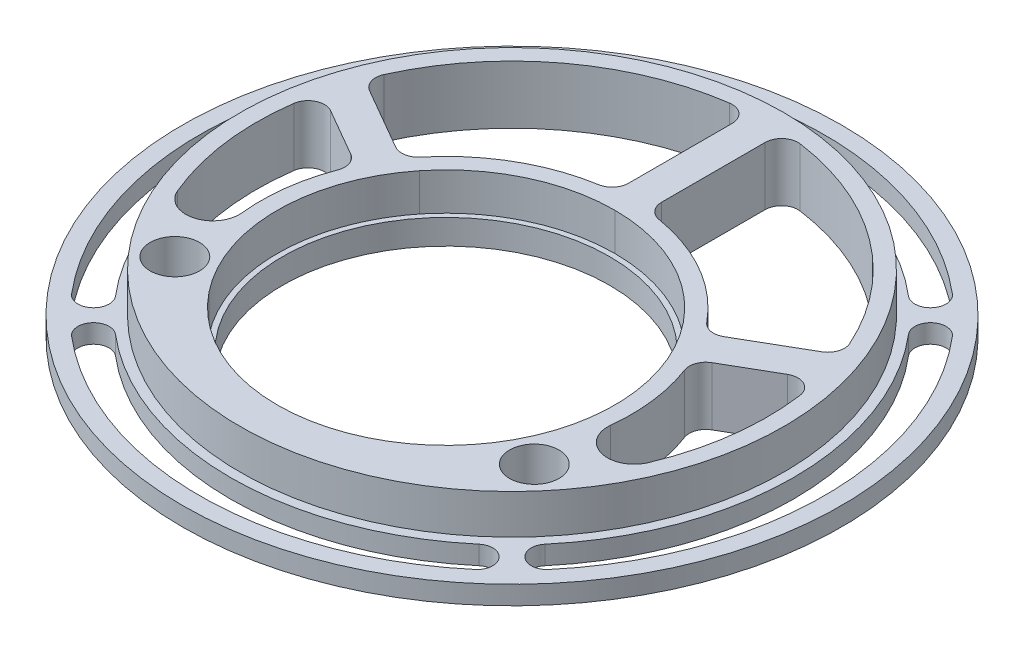
SolidWorks part; units mm, degrees
material "6061-T6 (SS)"
ref_plane "X-Y Datum" through (0, 0, 0) normal (0, 0, 1) x (1, 0, 0)
ref_plane "X-Z Datum" through (0, 0, 0) normal (0, 1, 0) x (1, 0, 0)
ref_plane "Y-Z Datum" through (0, 0, 0) normal (1, 0, 0) x (0, 0, -1)
sketch "Sketch1" plane through (0, 0, 0) normal (0, 1, 0) x (1, 0, 0)
  line L0 (0, 0) -> (0, -12.7) construction
  line L1 (0, -43.0151) -> (0, 43.0151) construction
  line L2 (0, 52.3875) -> (0, 61.9125) construction
  circle A0 centre (0, -12.7) radius 30.988
  circle A1 centre (0, 0) radius 52.3875 construction
  circle A2 centre (0, 0) radius 61.9125
  circle A3 centre (0, 0) radius 57.15 construction
  point P12 (0, 57.15)
  dimension "D2" = 61.976
  dimension "D3" = 104.775
  dimension "D4" = 123.825
  dimension "D5" = 114.3
  dimension "D1" = 12.7
extrude "Slotted-Body Extrude" add sketch "Sketch1" along normal blind 4.191 and the other way blind 0.2032
sketch "Sketch5" plane through (0, 4.191, 0) normal (0, 1, 0) x (1, 0, 0)
  circle A0 centre (0, 0) radius 52.3875 construction
  circle A1 centre (0, 0) radius 52.3875
extrude "Boss-Extrude3" add sketch "Sketch5" along normal blind 7.62
sketch "Sketch6" plane through (0, -0.2032, 0) normal (0, -1, 0) x (1, 0, 0)
  line L0 (0, -79.2756) -> (0, 0) construction
  circle A0 centre (0, 12.7) radius 30.988 construction
  circle A1 centre (0, 12.7) radius 30.988 construction
  circle A2 centre (0, 12.7) radius 32.512
  circle A21 centre (0, 0) radius 61.9125 construction
  dimension "D1" = 65.024
extrude "Cut-Extrude5" cut sketch "Sketch6" against normal through all
sketch "Sketch8" plane through (0, -0.2032, 0) normal (0, -1, 0) x (1, 0, 0)
  circle A0 centre (0, 12.7) radius 32.512 construction
  circle A1 centre (0, 12.7) radius 32.512
  circle A2 centre (0, 12.7) radius 31.496
  dimension "D1" = 62.992
extrude "Boss-Extrude4" add sketch "Sketch8" against normal blind 4.795 separate body
ref_point "Point1"
ref_plane "Plane1" through (0, 0, 0) normal (1, 0, 0) x (0, 0, -1)
split line "Split Line1"
ref_point "Point3"
ref_point "Point5"
ref_plane "Plane3" through (55.9011, 0, 0) normal (-1, 0, 0) x (0, 0, 1)
sketch "Sketch11" plane through (0, -0.2032, 0) normal (0, -1, 0) x (1, 0, 0)
  line L1 (-61.9125, -61.9125) -> (61.9125, -61.9125)
  line L2 (-61.9125, -61.9125) -> (-61.9125, 61.9125)
  line L3 (-61.9125, 61.9125) -> (61.9125, 61.9125)
  line L4 (61.9125, -61.9125) -> (61.9125, 61.9125)
  line L5 (-61.9125, -61.9125) -> (61.9125, 61.9125) construction
  line L6 (-61.9125, 61.9125) -> (61.9125, -61.9125) construction
  circle A0 centre (0, 0) radius 61.9125 construction
  point P0 (0, 0)
ref_point "Point6"
sketch "Sketch12" plane through (0, 4.191, 0) normal (0, 1, 0) x (1, 0, 0)
  line L0 (0, 0) -> (0, 57.2135)
  line L1 (0, -43.0151) -> (0, 43.0151) construction
  arc A0 (36.9549, 43.6775) -> (-36.9549, 43.6775) centre (0, 0) ccw construction
  arc A1 (38.8926, 45.9677) -> (-38.8926, 45.9677) centre (0, 0) ccw
  circle A2 centre (0, 0) radius 57.2135 construction
  arc A3 (-43.6775, 36.9549) -> (-43.6775, -36.9549) centre (0, 0) ccw construction
  arc A4 (-45.9677, 38.8926) -> (-45.9677, -38.8926) centre (0, 0) ccw
  arc A5 (-41.3872, 35.0171) -> (-41.3872, -35.0171) centre (0, 0) ccw
  arc A6 (-41.3872, 35.0171) -> (-45.9677, 38.8926) centre (-43.6775, 36.9549) ccw
  arc A7 (-45.9677, -38.8926) -> (-41.3872, -35.0171) centre (-43.6775, -36.9549) ccw
  arc A8 (35.0171, 41.3872) -> (-35.0171, 41.3872) centre (0, 0) ccw
  arc A9 (35.0171, 41.3872) -> (38.8926, 45.9677) centre (36.9549, 43.6775) ccw
  arc A10 (-38.8926, 45.9677) -> (-35.0171, 41.3872) centre (-36.9549, 43.6775) ccw
  arc A11 (43.6775, -36.9549) -> (43.6775, 36.9549) centre (0, 0) ccw construction
  arc A12 (45.9677, -38.8926) -> (45.9677, 38.8926) centre (0, 0) ccw
  arc A13 (41.3872, -35.0171) -> (41.3872, 35.0171) centre (0, 0) ccw
  arc A14 (41.3872, -35.0171) -> (45.9677, -38.8926) centre (43.6775, -36.9549) ccw
  arc A15 (45.9677, 38.8926) -> (41.3872, 35.0171) centre (43.6775, 36.9549) ccw
  arc A16 (-36.9549, -43.6775) -> (36.9549, -43.6775) centre (0, 0) ccw construction
  arc A17 (-38.8926, -45.9677) -> (38.8926, -45.9677) centre (0, 0) ccw
  arc A18 (-35.0171, -41.3872) -> (35.0171, -41.3872) centre (0, 0) ccw
  arc A19 (-35.0171, -41.3872) -> (-38.8926, -45.9677) centre (-36.9549, -43.6775) ccw
  arc A20 (38.8926, -45.9677) -> (35.0171, -41.3872) centre (36.9549, -43.6775) ccw
  point P3 (-57.2135, 0)
  point P10 (-41.7397, 39.2451)
  point P15 (0, 57.2135)
  point P22 (57.2135, 0)
  point P29 (0, -57.2135)
  point P34 (0, 0)
  dimension "D1" = 114.427
  dimension "D2" = 3
  dimension "D3" = 76.2
  dimension "D5" = 0
  dimension "D4" = 4
sketch "Sketch13" plane through (0, 11.811, 0) normal (0, 1, 0) x (1, 0, 0)
  line L0 (0, -12.7) -> (-58.2642, 20.9389)
  line L1 (1.5875, -9.9504) -> (-56.6767, 23.6885)
  line L2 (-1.5875, -15.4496) -> (-59.8517, 18.1892)
  line L3 (0, -12.7) -> (0, 52.3875)
  line L4 (1.5875, -15.4496) -> (59.8517, 18.1892)
  line L5 (0, -12.7) -> (58.2642, 20.9389)
  line L6 (-1.5875, -9.9504) -> (56.6767, 23.6885)
  line L7 (3.175, -12.7) -> (3.175, 52.3875)
  line L8 (-3.175, -12.7) -> (-3.175, 52.3875)
  line L9 (0, -43.0151) -> (0, 43.0151) construction
  circle A0 centre (0, 0) radius 52.3875
  circle A1 centre (0, 0) radius 52.3875 construction
  circle A2 centre (0, -12.7) radius 32.512
  circle A3 centre (0, -12.7) radius 32.512 construction
  circle A4 centre (0, 0) radius 61.9125 construction
  circle A5 centre (0, 0) radius 49.2125
  circle A6 centre (0, -12.7) radius 35.687
  circle A7 centre (-40.6121, -17.0686) radius 5.1594
  circle A8 centre (40.6121, -17.0686) radius 5.1594
  circle A9 centre (-34.6308, -30.3341) radius 3.175
  circle A10 centre (34.6308, -30.3341) radius 3.175
  dimension "D1" = 3.175
  dimension "D8" = 10.3187
  dimension "D9" = 6.35
  dimension "D3" = 3.175
  dimension "D5" = 60
  dimension "D2" = 3.175
  dimension "D4" = 3.175
  dimension "D6" = 3.175
  dimension "D7" = 3.175
extrude "Cut-Extrude7" cut sketch "Sketch13" against normal blind 36.068 contours A7 | A7 A6 L2 A5 | A6 L8 A5 L1 | A6 L6 A5 L7 | A6 A8 A5 L4 | A8 region at (-22.0763, 11.811, -28.9687) region at (-42.1402, 11.811, 2.4156) region at (22.0763, 11.811, -28.9687) region at (42.1402, 11.811, 2.4156) region at (-40.6121, 11.811, 17.0686) region at (40.6121, 11.811, 17.0686)
fillet "Fillet1" radius 3.175 12 edges at (47.9002, 5.8039, -11.289) (32.3708, 5.8039, -2.3231) (29.1958, 5.8039, -7.8224) (45.989, 5.8039, -17.518) (3.175, 5.8039, -49.11) (3.175, 5.8039, -22.8455) (-3.175, 5.8039, -22.8455) (-3.175, 5.8039, -49.11) (-45.989, 5.8039, -17.518) (-29.1958, 5.8039, -7.8224) (-32.3708, 5.8039, -2.3231) (-47.9002, 5.8039, -11.289)
extrude "Cut-Extrude8" cut sketch "Sketch12" against normal blind 36.068 contours A1 A10 A8 A9 | A12 A15 A13 A14 | A17 A20 A18 A19 | A4 A7 A5 A6 region at (38.6171, 4.191, -42.2711) region at (-42.2711, 4.191, -38.6171) region at (42.2711, 4.191, 38.6171) region at (-38.6171, 4.191, 42.2711)
ref_plane "Plane4" through (25.4, 0, 0) normal (1, 0, 0) x (0, 0, -1)
ref_plane "Plane5" through (-25.4, 0, 0) normal (1, 0, 0) x (0, 0, -1)
split line "Split Line3"
split line "Split Line4"
other "Move Face1" face at (0, -0.2032, 61.9125) offset 1.5875 parameters "D1"=1.5875
other "Move Face2" flip direction yes face at (0, -0.2032, -49.4766) offset 0.7937 parameters "D1"=0.7937
extrude "Cut-Extrude9" cut sketch "Sketch13<5>" against normal through all contours A9 | A10 region at (-34.6308, 11.811, 30.3341) region at (34.6308, 11.811, 30.3341)
sketch "Sketch13<5>" plane through (0, 11.811, 0) normal (0, 1, 0) x (1, 0, 0) same geometry as "Sketch13"
other "Move Face3" flip direction yes face at (34.6308, 11.811, 33.5091) face at (-34.6308, 11.811, 33.5091) offset 1.5875 parameters "D1"=1.5875
